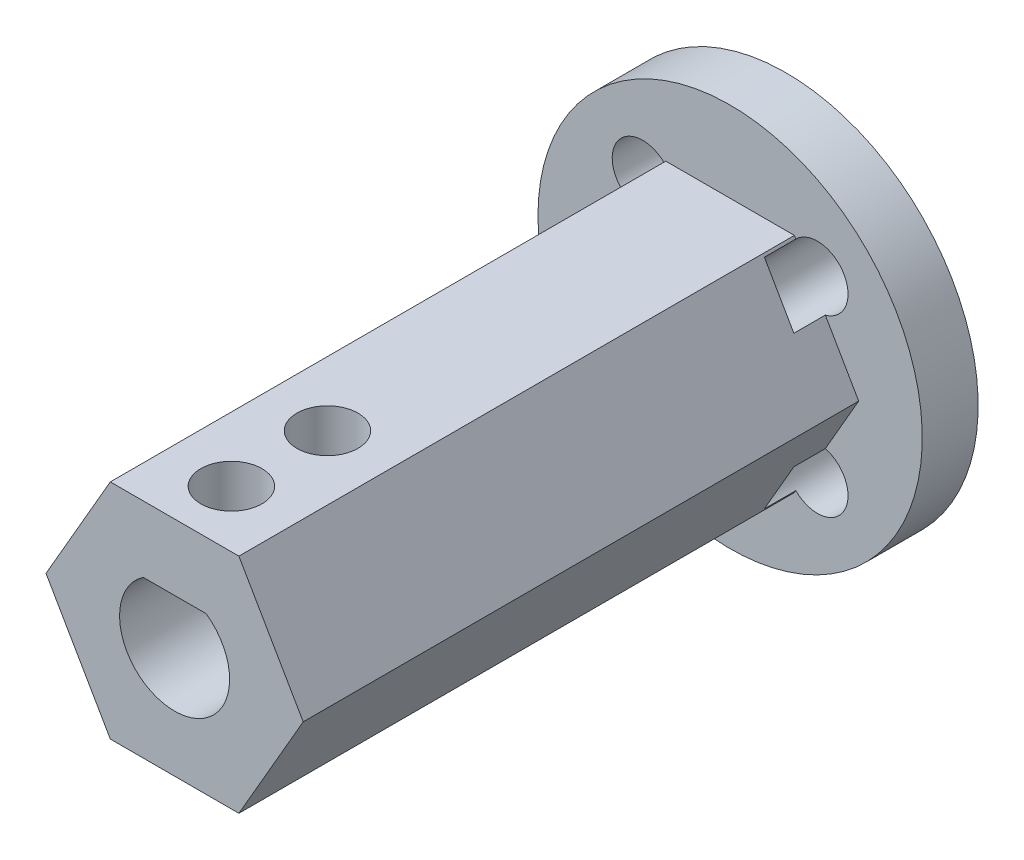
SolidWorks part; units mm, degrees
ref_plane "Alzado" through (0, 0, 0) normal (0, 0, 1) x (1, 0, 0)
ref_plane "Planta" through (0, 0, 0) normal (0, 1, 0) x (1, 0, 0)
ref_plane "Vista lateral" through (0, 0, 0) normal (1, 0, 0) x (0, 0, -1)
sketch "Croquis1" plane through (0, 0, 0) normal (0, 0, 1) x (1, 0, 0)
  line L0 (0, 0) -> (0, 2.5851) construction
  line L1 (7.3617, 0) -> (3.6808, 6.3754)
  line L2 (3.6808, 6.3754) -> (-3.6808, 6.3754)
  line L3 (-3.6808, 6.3754) -> (-7.3617, 0)
  line L4 (-7.3617, 0) -> (-3.6808, -6.3754)
  line L5 (-3.6808, -6.3754) -> (3.6808, -6.3754)
  line L6 (3.6808, -6.3754) -> (7.3617, 0)
  line L7 (-1.8, 2.5851) -> (1.8, 2.5851)
  circle A0 centre (0, 0) radius 6.3754 construction
  arc A1 (-1.8, 2.5851) -> (1.8, 2.5851) centre (0, 0) ccw
  point P14 (0, 2.5851)
  dimension "D2" = 6.3
  dimension "D1" = 12.7508
  dimension "D3" = 3.6
extrude "Saliente-Extruir1" add sketch "Croquis1" along normal blind 35
sketch "Croquis2" plane through (0, 6.3754, 0) normal (0, 1, 0) x (1, 0, 0)
  line L0 (0, -35) -> (0, -31.75) construction
  line L1 (3.6808, -35) -> (-3.6808, -35) construction
  line L2 (0, -31.75) -> (0, -30) construction
  line L3 (0, -30) -> (0, -28) construction
  line L4 (0, -28) -> (0, -26.25) construction
  line L5 (0, -26.25) -> (0, -23) construction
  circle A0 centre (0, -31.75) radius 1.75
  circle A1 centre (0, -26.25) radius 1.75
  dimension "D1" = 3.5
  dimension "D2" = 12
  dimension "D3" = 2
extrude "Cortar-Extruir1" cut sketch "Croquis2" against normal blind 7.5
sketch "Croquis3" plane through (0, 0, 0) normal (0, 0, -1) x (-1, 0, 0)
  circle A0 centre (0, 0) radius 11
  dimension "D1" = 22
extrude "Saliente-Extruir2" add sketch "Croquis3" against normal blind 3.2
sketch "Croquis5" plane through (0, 0, 0) normal (0, 0, -1) x (-1, 0, 0)
  line L0 (0, 0) -> (0, 5) construction
  line L1 (0, 5) -> (-5, 5) construction
  circle A0 centre (-5, 5) radius 1.75
  circle A1 centre (5, 5) radius 1.75
  circle A2 centre (5, -5) radius 1.75
  circle A3 centre (-5, -5) radius 1.75
  point P14 (0, 0)
  dimension "D3" = 3.5
  dimension "D1" = 5
  dimension "D2" = 5
  dimension "D5" = 10
  dimension "D4" = 4
extrude "Cortar-Extruir2" cut sketch "Croquis5" against normal blind 5 and the other way through all
